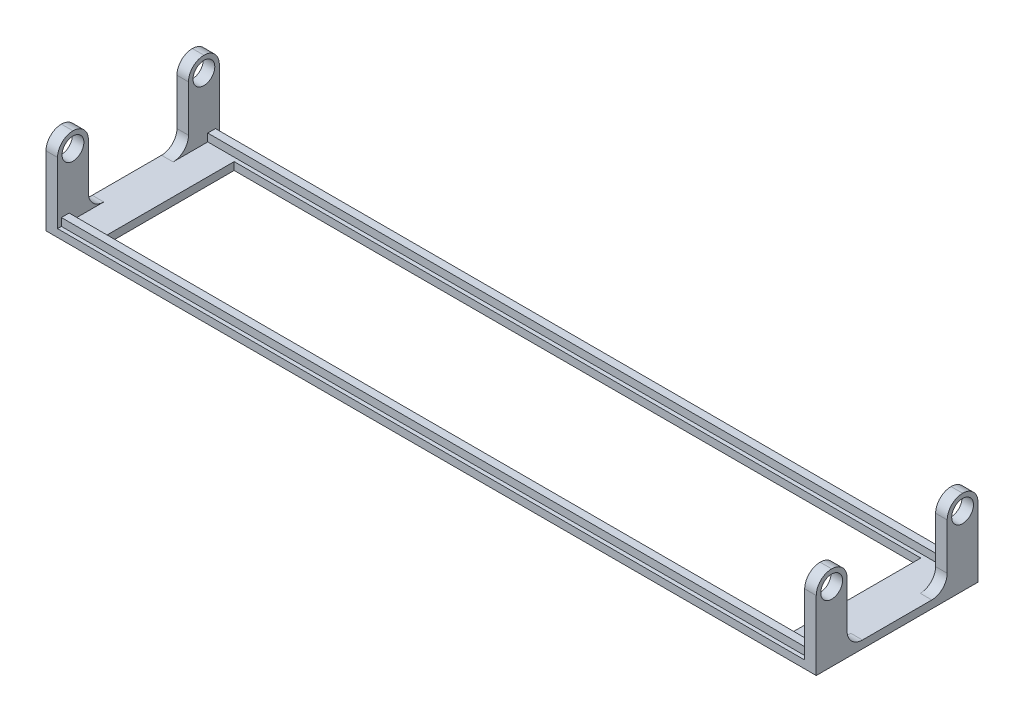
SolidWorks part; units mm, degrees
ref_plane "Front Plane" through (0, 0, 0) normal (0, 0, 1) x (1, 0, 0)
ref_plane "Top Plane" through (0, 0, 0) normal (0, 1, 0) x (1, 0, 0)
ref_plane "Right Plane" through (0, 0, 0) normal (1, 0, 0) x (0, 0, -1)
sketch "Sketch1" plane through (0, 0, 0) normal (0, 1, 0) x (1, 0, 0)
  line L1 (-1000, -210) -> (1000, -210)
  line L2 (-1000, -210) -> (-1000, 210)
  line L3 (-1000, 210) -> (1000, 210)
  line L4 (1000, -210) -> (1000, 210)
  line L5 (-1000, -210) -> (1000, 210) construction
  line L6 (-1000, 210) -> (1000, -210) construction
  line L7 (891.47, -170) -> (-891.47, -170)
  line L8 (891.47, -170) -> (891.47, 170)
  line L9 (891.47, 170) -> (-891.47, 170)
  line L10 (-891.47, -170) -> (-891.47, 170)
  line L11 (891.47, -170) -> (-891.47, 170) construction
  line L12 (891.47, 170) -> (-891.47, -170) construction
  point P0 (0, 0)
  point P6 (0, 0)
extrude "Boss-Extrude1" add sketch "Sketch1" along normal blind 20
sketch "Sketch3" plane through (0, 20, 0) normal (0, 1, 0) x (1, 0, 0)
  line L0 (-970, 210) -> (-970, 130)
  line L1 (1000, -210) -> (970, -210)
  line L2 (1000, -210) -> (1000, -130)
  line L3 (1000, -130) -> (970, -130)
  line L4 (970, -210) -> (970, -130)
  line L5 (1000, 210) -> (970, 210)
  line L6 (1000, 210) -> (1000, 130)
  line L7 (1000, 130) -> (970, 130)
  line L8 (970, 210) -> (970, 130)
  line L9 (-1000, 130) -> (-970, 130)
  line L10 (-1000, 210) -> (-970, 210)
  line L11 (-1000, 210) -> (-1000, 130)
  line L12 (-1000, -210) -> (-970, -210)
  line L13 (-970, -210) -> (-970, -130)
  line L14 (-1000, -210) -> (-1000, -130)
  line L15 (-1000, -130) -> (-970, -130)
  point P20 (0, 0)
  dimension "D1" = 2
extrude "Boss-Extrude2" add sketch "Sketch3" along normal blind 200
fillet "Fillet1" radius 40 8 edges at (-985, 220, -210) (-985, 220, -130) (-985, 220, 130) (-985, 220, 210) (985, 220, -210) (985, 220, -130) (985, 220, 130) (985, 220, 210)
fillet "Fillet2" radius 40 4 edges at (985, 20, 130) (985, 20, -130) (-985, 20, 130) (-985, 20, -130)
sketch "Sketch5" plane through (0, 20, 0) normal (0, 1, 0) x (1, 0, 0)
  line L0 (0, -170) -> (0, -210)
  line L1 (-891.47, -170) -> (891.47, -170) construction
  line L2 (-970, -210) -> (970, -210) construction
  line L3 (-972.3781, 200.0109) -> (-972.3781, 179.9891)
  line L4 (972.3781, -200.0109) -> (-972.3781, -200.0109)
  line L5 (972.3781, -200.0109) -> (972.3781, -179.9891)
  line L6 (972.3781, -179.9891) -> (-972.3781, -179.9891)
  line L7 (-972.3781, -200.0109) -> (-972.3781, -179.9891)
  line L8 (972.3781, -200.0109) -> (-972.3781, -179.9891) construction
  line L9 (972.3781, -179.9891) -> (-972.3781, -200.0109) construction
  line L10 (-972.3781, 179.9891) -> (972.3781, 179.9891)
  line L11 (-972.3781, 200.0109) -> (972.3781, 200.0109)
  line L12 (972.3781, 200.0109) -> (972.3781, 179.9891)
  point P6 (0, -190)
  point P17 (0, 0)
  dimension "D1" = 2
extrude "Boss-Extrude5" add sketch "Sketch5" along normal blind 20 contours L5 L6 L0 L4 | L12 L11 L3 L10 | L7 L4 L0 L6 region at (486.1891, 20, 190) region at (-486.1891, 20, 190) region at (0, 20, -190)
sketch "Sketch9" plane through (970, 0, 0) normal (-1, 0, 0) x (0, 0, 1)
  circle A0 centre (-170, 180) radius 28.2843
  circle A1 centre (170, 180) radius 28.2843
extrude "Cut-Extrude3" cut sketch "Sketch9" against normal blind 85 and the other way blind 2088
